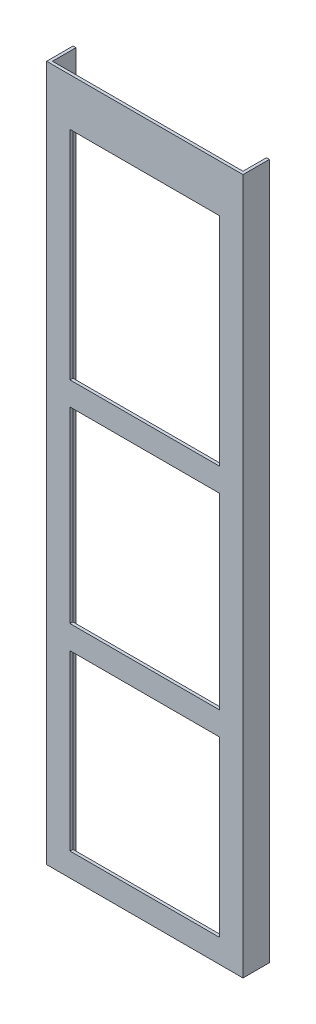
SolidWorks part; units mm, degrees
material "6061-T6 (SS)"
ref_plane "Front Plane" through (0, 0, 0) normal (0, 0, 1) x (1, 0, 0)
ref_plane "Top Plane" through (0, 0, 0) normal (0, 1, 0) x (1, 0, 0)
ref_plane "Right Plane" through (0, 0, 0) normal (1, 0, 0) x (0, 0, -1)
sketch "Sketch1" plane through (0, 0, 0) normal (0, 1, 0) x (1, 0, 0)
  line L0 (0, 50) -> (0, 41.5) construction
  line L1 (-50, 0) -> (-41.5, 0) construction
  line L2 (-50, 0) -> (-50, 50) construction
  line L3 (-50, 50) -> (50, 50) construction
  line L4 (50, 50) -> (50, -50) construction
  line L5 (50, -50) -> (-50, -50) construction
  line L6 (-50, -50) -> (-50, 0) construction
  line L7 (-41.5, 50) -> (-41.5, -50) construction
  line L8 (41.5, 50) -> (41.5, -50) construction
  line L9 (-50, 41.5) -> (50, 41.5) construction
  line L10 (-50, -41.5) -> (50, -41.5) construction
  line L11 (51.5875, 51.5875) -> (-51.5875, 51.5875)
  line L12 (50, 50) -> (-50, 50)
  line L13 (50, 50) -> (50, -50)
  line L14 (50, -50) -> (-50, -50)
  line L15 (-50, 50) -> (-50, -50)
  line L16 (-51.5875, 51.5875) -> (-51.5875, -51.5875)
  line L17 (51.5875, -51.5875) -> (-51.5875, -51.5875)
  line L18 (51.5875, 51.5875) -> (51.5875, -51.5875)
  line L47 (41.5, 0) -> (50, 0) construction
  line L52 (0, -41.5) -> (0, -50) construction
  circle A0 centre (0, 0) radius 76.2 construction
  dimension "D4" = 152.4
  dimension "D1" = 1.5875
extrude "BulkShellExtrude" add sketch "Sketch1" along normal blind 376.8
sketch "AirframeReferenceBottom" plane through (0, 0, 0) normal (0, 1, 0) x (1, 0, 0)
  circle A0 centre (0, 0) radius 76.2 construction
  dimension "D1" = 152.4
sketch "AxialReference" plane through (0, 0, 0) normal (1, 0, 0) x (0, 0, -1)
  line L0 (0, 0) -> (0, 376.8) construction
  line L1 (-51.5875, 376.8) -> (51.5875, 376.8) construction
sketch "AirframeReferenceTop" plane through (0, 376.8, 0) normal (0, 1, 0) x (1, 0, 0)
  circle A0 centre (0, 0) radius 76.2 construction
  dimension "D1" = 152.4
sketch "Sketch14" plane through (51.5875, 0, 0) normal (1, 0, 0) x (0, 0, -1)
  line L0 (-51.5875, 376.8) -> (-51.5875, 0) construction
  line L1 (-38.8875, 364.1) -> (38.8875, 364.1)
  line L2 (-38.8875, 364.1) -> (-38.8875, 12.7)
  line L3 (-38.8875, 12.7) -> (38.8875, 12.7)
  line L4 (38.8875, 364.1) -> (38.8875, 12.7)
  line L5 (51.5875, 376.8) -> (51.5875, 0) construction
  line L6 (76.2, 376.8) -> (-76.2, 376.8) construction
  line L7 (76.2, 0) -> (-76.2, 0) construction
  dimension "D1" = 12.7
  dimension "D2" = 12.7
  dimension "D3" = 12.7
  dimension "D4" = 12.7
extrude "SideWallCut" cut sketch "Sketch14" against normal blind 103.1875
sketch "Sketch22" plane through (51.5875, 0, 0) normal (1, 0, 0) x (0, 0, -1)
  line L0 (76.2, 0) -> (-76.2, 0) construction
  line L1 (-51.5875, 376.8) -> (-50, 376.8) construction
  line L2 (-51.5875, 376.8) -> (-51.5875, 0) construction
  line L3 (-51.5875, 0) -> (-50, 0) construction
  line L4 (-50, 376.8) -> (-50, 0) construction
  line L5 (76.2, 376.8) -> (-76.2, 376.8) construction
  line L6 (51.5875, 0) -> (50, 0) construction
  line L7 (51.5875, 0) -> (51.5875, 376.8) construction
  line L8 (51.5875, 376.8) -> (50, 376.8) construction
  line L9 (50, 0) -> (50, 376.8) construction
  line L11 (-50, 376.8) -> (50, 376.8)
  line L12 (-50, 376.8) -> (-50, 0)
  line L13 (-50, 0) -> (50, 0)
  line L14 (50, 376.8) -> (50, 0)
  dimension "D1" = 1.5875
  dimension "D2" = 1.5875
extrude "Cut-Extrude4" cut sketch "Sketch22" against normal blind 103.1875
sketch "Sketch23" plane through (51.5875, 0, 0) normal (1, 0, 0) x (0, 0, -1)
  line L1 (-51.5875, 376.8) -> (-50, 376.8)
  line L2 (-51.5875, 376.8) -> (-51.5875, 0)
  line L3 (-51.5875, 0) -> (-50, 0)
  line L4 (-50, 376.8) -> (-50, 0)
extrude "Boss-Extrude1" add sketch "Sketch23" along normal blind 1.5875
mirror "Mirror1" about plane through (0, 0, 0) normal (1, 0, 0) of "Boss-Extrude1"
sketch "Sketch24" plane through (0, 0, 50) normal (0, 0, -1) x (-1, 0, 0)
  line L0 (76.2, 0) -> (-76.2, 0) construction
  line L1 (-53.175, 376.8) -> (-51.5875, 376.8)
  line L2 (-53.175, 376.8) -> (-53.175, 0)
  line L3 (-53.175, 0) -> (-51.5875, 0)
  line L4 (-51.5875, 376.8) -> (-51.5875, 0)
  line L6 (53.175, 376.8) -> (51.5875, 376.8)
  line L7 (53.175, 376.8) -> (53.175, 0)
  line L8 (53.175, 0) -> (51.5875, 0)
  line L9 (51.5875, 376.8) -> (51.5875, 0)
  dimension "D1" = 1.5875
  dimension "D2" = 1.5875
extrude "Boss-Extrude2" add sketch "Sketch24" along normal blind 12.7
sketch "Sketch25" plane through (0, 0, 51.5875) normal (0, 0, 1) x (1, 0, 0)
  line L0 (0, 0) -> (0, 376.8) construction
  line L1 (40.475, 12.7) -> (-40.475, 12.7)
  line L2 (40.475, 12.7) -> (40.475, 364.1)
  line L3 (40.475, 364.1) -> (-40.475, 364.1)
  line L4 (-40.475, 12.7) -> (-40.475, 364.1)
  line L5 (40.475, 12.7) -> (-40.475, 364.1) construction
  line L6 (40.475, 364.1) -> (-40.475, 12.7) construction
  line L7 (-53.175, 376.8) -> (-53.175, 0) construction
  line L8 (76.2, 376.8) -> (-76.2, 376.8) construction
  point P0 (0, 188.4)
  dimension "D1" = 12.7
  dimension "D2" = 12.7
extrude "Cut-Extrude5" cut sketch "Sketch25" against normal blind 2.54
sketch "Sketch26" plane through (0, 0, 51.5875) normal (0, 0, 1) x (1, 0, 0)
  line L0 (0, 0) -> (0, 376.8) construction
  line L1 (76.2, 376.8) -> (-76.2, 376.8) construction
  line L2 (-53.175, 113.03) -> (53.175, 113.03) construction
  line L3 (-53.175, 376.8) -> (-53.175, 0) construction
  line L4 (53.175, 376.8) -> (53.175, 0) construction
  line L5 (76.2, 0) -> (-76.2, 0) construction
  line L6 (-53.175, 227.33) -> (53.175, 227.33) construction
  line L7 (-53.175, 220.98) -> (53.175, 220.98)
  line L8 (-53.175, 106.68) -> (53.175, 106.68)
  line L9 (-53.175, 233.68) -> (53.175, 233.68)
  line L10 (-53.175, 119.38) -> (53.175, 119.38)
  line L11 (-53.175, 351.155) -> (53.175, 351.155) construction
  line L12 (40.475, 12.7) -> (-40.475, 12.7)
  line L13 (40.475, 12.7) -> (40.475, 364.1)
  line L14 (40.475, 364.1) -> (-40.475, 364.1)
  line L15 (-40.475, 12.7) -> (-40.475, 364.1)
  line L16 (40.475, 12.7) -> (-40.475, 364.1) construction
  line L17 (40.475, 364.1) -> (-40.475, 12.7) construction
  line L19 (-40.475, 351.155) -> (40.475, 351.155)
  line L20 (-40.475, 351.155) -> (-40.475, 364.1)
  line L21 (-40.475, 364.1) -> (40.475, 364.1)
  line L22 (40.475, 351.155) -> (40.475, 364.1)
  point P23 (0, 188.4)
  line M5 (-40.475, 12.7) -> (-40.475, 364.1)
  line M6 (-40.475, 364.1) -> (40.475, 364.1)
  line M7 (40.475, 364.1) -> (40.475, 12.7)
  dimension "D1" = 113.03
  dimension "D2" = 227.33
  dimension "D5" = 351.155
  dimension "D3" = 6.35
  dimension "D4" = 6.35
extrude "Boss-Extrude3" add sketch "Sketch26" against normal blind 1.5875 contours L15 L19 M7 M6 | L9 L7 M5 M7 | L10 L8 M5 M7 region at (0, 227.33, 51.5875) region at (0, 113.03, 51.5875) region at (0, 357.6275, 51.5875)
